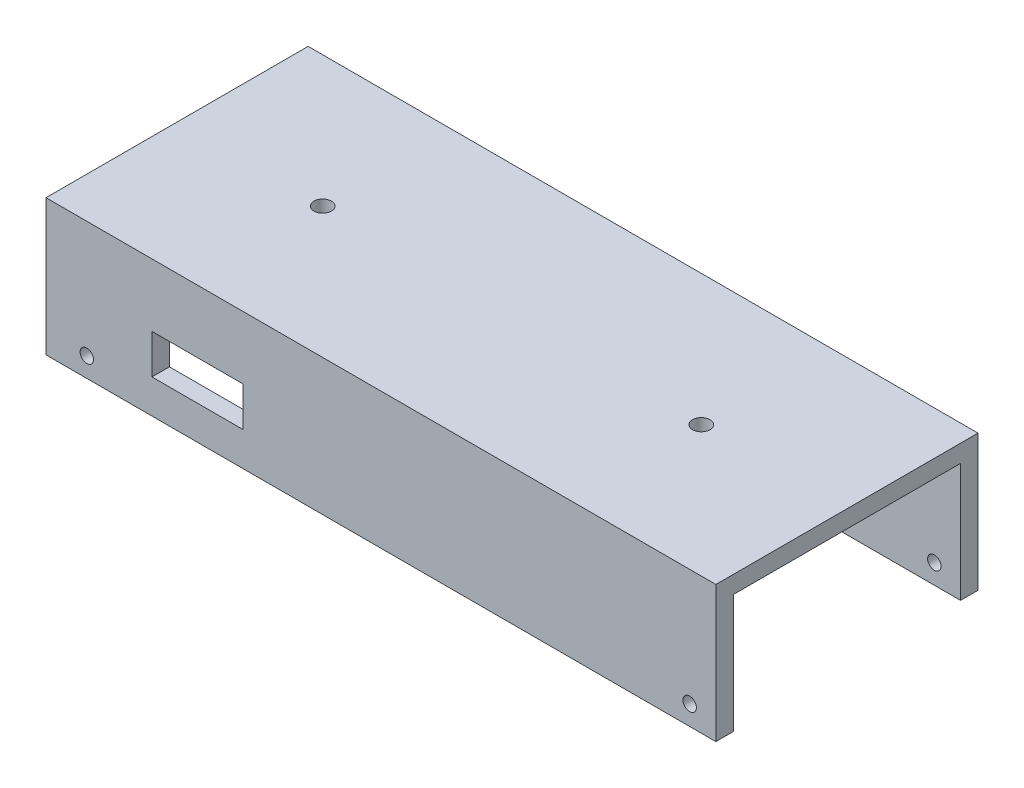
SolidWorks part; units mm, degrees
ref_plane "Front Plane" through (0, 0, 0) normal (0, 0, 1) x (1, 0, 0)
ref_plane "Top Plane" through (0, 0, 0) normal (0, 1, 0) x (1, 0, 0)
ref_plane "Right Plane" through (0, 0, 0) normal (1, 0, 0) x (0, 0, -1)
sketch "Sketch1" plane through (0, 0, 0) normal (0, 0, 1) x (1, 0, 0)
  line L9 (21.172, -17.9478) -> (91.172, -17.9478)
  line L10 (21.172, -17.9478) -> (21.172, -40.3878)
  line L11 (4.5, -8) -> (200.727, -8) construction
  line L12 (4.5, -8) -> (-67.0185, -8) construction
  line L13 (21.172, -40.3878) -> (91.172, -40.3878)
  line L14 (91.172, -17.9478) -> (91.172, -40.3878)
  line L15 (0, 0) -> (115, 0)
  line L16 (0, 0) -> (0, 27)
  line L17 (0, 27) -> (115, 27)
  line L18 (115, 0) -> (115, 27)
  circle A0 centre (4.5, 7) radius 1.15
  circle A1 centre (4.5, 7) radius 15 construction
  circle A3 centre (77.172, -29.1678) radius 3.6067
  circle A4 centre (110.5, 7) radius 15 construction
  circle A5 centre (110.5, 7) radius 1.15
  point P19 (21.172, -29.1678)
  dimension "D4" = 30
  dimension "D2" = 14
  dimension "D7" = 30
  dimension "D11" = 4.5
  dimension "D13" = 2.3
  dimension "D14" = 2.3
  dimension "D3" = 70
  dimension "D5" = 22.44
  dimension "D6" = 115
  dimension "D8" = 27
  dimension "D9" = 4.5
  dimension "D10" = 7
  dimension "D12" = 7
extrude "Boss-Extrude5" add sketch "Sketch1" along normal blind 45 contours L16 L15 L18 L17
shell "Shell9" thickness 3 removed face at (115, 13.5, 22.5) removed face at (57.5, 0, 22.5) removed face at (0, 13.5, 22.5)
sketch "Sketch3" plane through (0, 0, 0) normal (0, 0, -1) x (-1, 0, 0)
  line L0 (0, 0) -> (-115, 0) construction
  line L1 (-115, 0) -> (-115, 27) construction
  line L2 (0, 0) -> (0, 27) construction
  circle A0 centre (-7, 7) radius 1.15
  circle A1 centre (-110.5, 7) radius 1.15
  dimension "D1" = 2.3
  dimension "D2" = 2.3
  dimension "D3" = 7
  dimension "D4" = 4.5
  dimension "D5" = 7
  dimension "D6" = 7
extrude "Cut-Extrude2" cut sketch "Sketch3" against normal blind 79
sketch "Sketch6" plane through (0, 0, 0) normal (0, 0, -1) x (-1, 0, 0)
  line L0 (-74.3435, 19.4061) -> (-45.0435, 19.4061) construction
  line L1 (-74.3435, 21.1561) -> (-45.0435, 21.1561)
  line L2 (-74.3435, 17.6561) -> (-45.0435, 17.6561)
  line L3 (-103.8735, 24.2807) -> (-33.8735, 24.2807) construction
  line L4 (-103.8735, 24.2807) -> (-103.8735, 1.8407) construction
  line L5 (-103.8735, 1.8407) -> (-33.8735, 1.8407) construction
  line L6 (-33.8735, 24.2807) -> (-33.8735, 1.8407) construction
  line L7 (0, 0) -> (-115, 0) construction
  line L8 (-89.8735, 13.0607) -> (-60.5735, 13.0607) construction
  line L9 (-89.8735, 16.0607) -> (-60.5735, 16.0607)
  line L10 (-89.8735, 10.0607) -> (-60.5735, 10.0607)
  line L11 (-60.5735, 13.0607) -> (-17.326, 13.0607) construction
  line L12 (-74.3435, 6.7152) -> (-45.0435, 6.7152) construction
  line L13 (-74.3435, 4.9652) -> (-45.0435, 4.9652)
  line L14 (-74.3435, 8.4652) -> (-45.0435, 8.4652)
  line L15 (0, 0) -> (0, 27) construction
  line L16 (-116.1483, -35.1917) -> (-46.1483, -35.1917)
  line L17 (-116.1483, -35.1917) -> (-116.1483, -57.6317)
  line L18 (-116.1483, -57.6317) -> (-46.1483, -57.6317)
  line L19 (-46.1483, -35.1917) -> (-46.1483, -57.6317)
  arc A1 (-89.8735, 16.0607) -> (-89.8735, 10.0607) centre (-89.8735, 13.0607) ccw
  circle A2 centre (-78.6235, 14.7223) radius 3.9722 construction
  circle A3 centre (-74.3435, 19.4061) radius 1.5 construction
  arc A4 (-89.8735, 16.0607) -> (-89.8735, 10.0607) centre (-89.8735, 13.0607) ccw
  arc A5 (-74.3435, 21.1561) -> (-74.3435, 17.6561) centre (-74.3435, 19.4061) ccw
  arc A6 (-45.0435, 17.6561) -> (-45.0435, 21.1561) centre (-45.0435, 19.4061) ccw
  arc A7 (-60.5735, 10.0607) -> (-60.5735, 16.0607) centre (-60.5735, 13.0607) ccw
  arc A8 (-74.3435, 4.9652) -> (-74.3435, 8.4652) centre (-74.3435, 6.7152) cw
  arc A9 (-45.0435, 8.4652) -> (-45.0435, 4.9652) centre (-45.0435, 6.7152) cw
  circle A10 centre (-81.5683, -40.0617) radius 1.5 construction
  point P6 (-103.8735, 13.0607)
  point P11 (-59.6935, 19.4061)
  point P19 (-75.2235, 13.0607)
  point P31 (-59.6935, 6.7152)
  point P42 (0, 0)
  point P43 (-73.9239, 19.4061)
  point P44 (-108.4053, -23.9085)
  point P45 (-69.0235, 19.4061)
  point P47 (-44.6257, 19.4061)
  point P48 (0, 0)
  point P49 (-7.9959, -18.3076)
  point P50 (20.5748, -37.3736)
  point P51 (-81.1483, -40.0617)
  dimension "D3" = 6
  dimension "D7" = 3
  dimension "D8" = 1.75
  dimension "D13" = 3
  dimension "D1" = 70
  dimension "D2" = 22.44
  dimension "D4" = 14
  dimension "D5" = 11.25
  dimension "D6" = 4.28
  dimension "D9" = 29.3
  dimension "D11" = 17.5654
  dimension "D12" = 19.4061
  dimension "D14" = 29.3
  dimension "D15" = 70
  dimension "D16" = 22.44
  dimension "D17" = 17.57
  dimension "D18" = 34.58
  dimension "D10" = 89.8735
extrude "Cut-Extrude8" cut sketch "Sketch6" against normal blind 23 contours L10 A7 L9 A1 | L2 A6 L1 A5 | L13 A9 L14 A8 region at (59.6935, 19.4061, 0) region at (75.2235, 13.0607, 0)
sketch "Sketch7" plane through (0, 0, 45) normal (0, 0, 1) x (1, 0, 0)
  line L1 (18.1879, 16.2216) -> (33.7918, 16.2216)
  line L2 (18.1879, 16.2216) -> (18.1879, 9.4478)
  line L3 (18.1879, 9.4478) -> (33.7918, 9.4478)
  line L4 (33.7918, 16.2216) -> (33.7918, 9.4478)
extrude "Cut-Extrude9" cut sketch "Sketch7" against normal blind 20
sketch "Sketch9" plane through (0, 24, 0) normal (0, -1, 0) x (1, 0, 0)
  line L0 (0, 20.1086) -> (115, 20.1086) construction
  line L1 (0, 42) -> (0, 3) construction
  line L2 (115, 42) -> (115, 3) construction
  text T0 "group 2"
extrude "Cut-Extrude10" cut sketch "Sketch9" against normal blind 1
sketch "Sketch10" plane through (0, 24, 0) normal (0, -1, 0) x (1, 0, 0)
  line L0 (0, 42) -> (0, 3) construction
  line L1 (115, 42) -> (115, 3) construction
  circle A0 centre (25, 22.5) radius 1.5
  circle A1 centre (90, 22.5) radius 1.5
  point P8 (115, 22.5)
  dimension "D3" = 3
  dimension "D4" = 3
  dimension "D1" = 25
  dimension "D2" = 25
extrude "Cut-Extrude11" cut sketch "Sketch10" against normal blind 26
sketch "Sketch11" plane through (0, 0, 0) normal (0, 0, -1) x (-1, 0, 0)
  line L0 (0, 0) -> (0, 27) construction
  line L1 (-115, 0) -> (0, 0)
  line L2 (-115, 0) -> (-115, 3.6307)
  line L3 (-115, 3.6307) -> (0, 3.6307)
  line L4 (0, 0) -> (0, 3.6307)
  dimension "D1" = 3.6307
extrude "Cut-Extrude12" cut sketch "Sketch11" against normal blind 68
equation "\"slot­_width\"=29.3"
equation "\"D9@Sketch6\"=\"slot­_width\""
equation "\"D14@Sketch6\"=\"slot­_width\""
